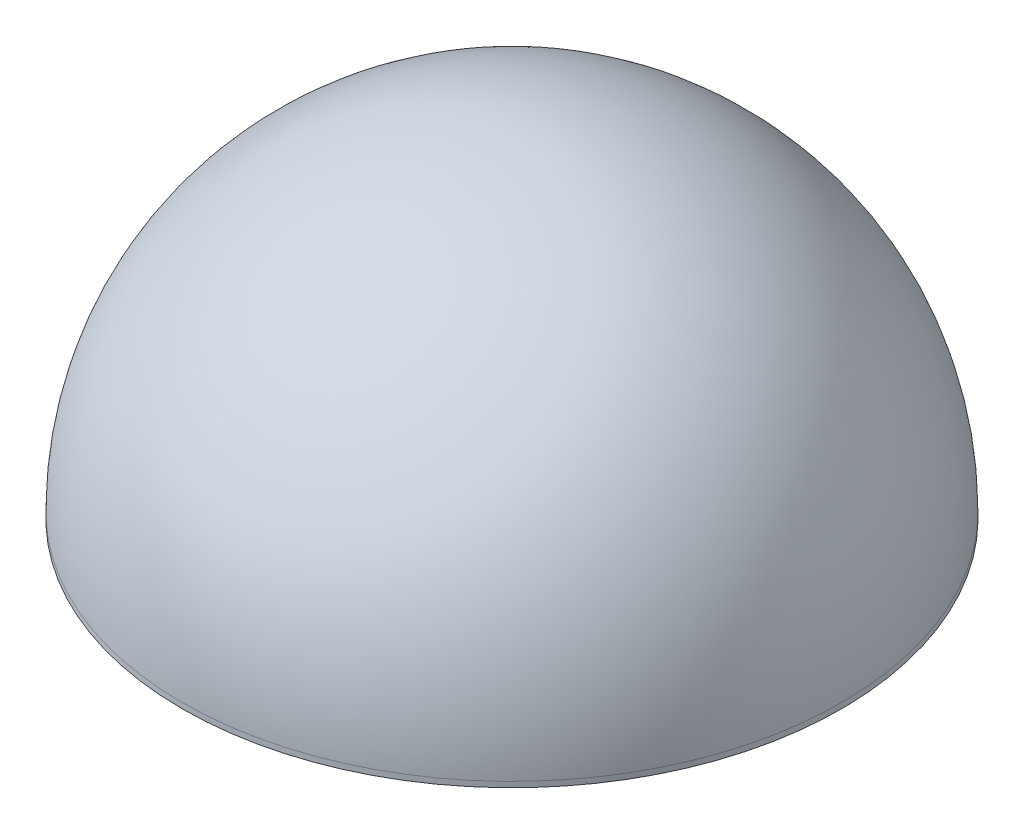
SolidWorks part; units mm, degrees
ref_plane "Front Plane" through (0, 0, 0) normal (0, 0, 1) x (1, 0, 0)
ref_plane "Top Plane" through (0, 0, 0) normal (0, 1, 0) x (1, 0, 0)
ref_plane "Right Plane" through (0, 0, 0) normal (1, 0, 0) x (0, 0, -1)
sketch "Sketch1" plane through (0, 0, 0) normal (0, 1, 0) x (1, 0, 0)
  circle A0 centre (0, 0) radius 152.4
extrude "Boss-Extrude1" add sketch "Sketch1" along normal blind 2.54
dome "Dome1" faces to dome 1 distance 152.4 reverse direction no elliptical dome no face at (0, 2.54, 152.4) parameters "D1"=152.4
